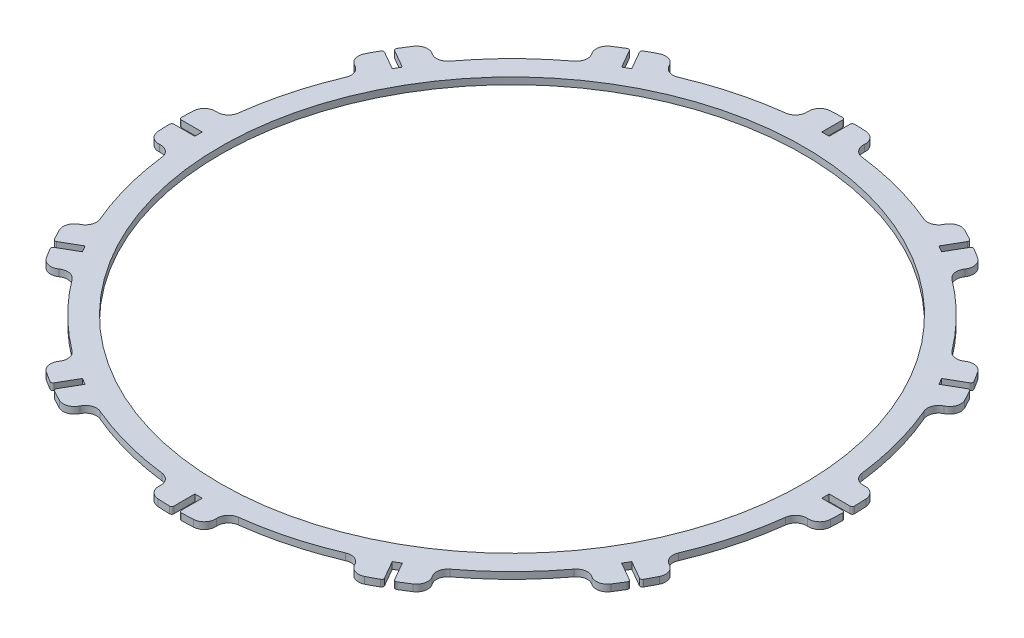
SolidWorks part; units mm, degrees
ref_plane "Front Plane" through (0, 0, 0) normal (0, 0, 1) x (1, 0, 0)
ref_plane "Top Plane" through (0, 0, 0) normal (0, 1, 0) x (1, 0, 0)
ref_plane "Right Plane" through (0, 0, 0) normal (1, 0, 0) x (0, 0, -1)
sketch "Sketch1" plane through (0, 0, 0) normal (0, 1, 0) x (1, 0, 0)
  line L1 (0, 130) -> (0, 150) construction
  circle A0 centre (0, 0) radius 150
  circle A1 centre (0, 0) radius 130
  point P7 (0, 0)
  dimension "D1" = 300
  dimension "D2" = 20
extrude "Boss-Extrude1" add sketch "Sketch1" along normal blind 3
sketch "Sketch2" plane through (0, 3, 0) normal (0, 1, 0) x (1, 0, 0)
  line L0 (0, 0) -> (0, 150) construction
  line L1 (-1.65, 139.7) -> (1.65, 139.7)
  line L2 (-1.65, 139.7) -> (-1.65, 152.3249)
  line L3 (-1.65, 152.3249) -> (1.65, 152.3249)
  line L4 (1.65, 152.3249) -> (1.65, 139.7)
  circle A0 centre (0, 0) radius 150 construction
  point P8 (0, 139.7)
  dimension "D1" = 139.7
  dimension "D2" = 3.3
extrude "Cut-Extrude1" cut sketch "Sketch2" against normal blind 3
fillet "Fillet1" radius 1 2 edges at (1.65, 1.5, -149.9909) (-1.65, 1.5, -149.9909)
pattern_circular "CirPattern1" count 12 over 360 about axis through (0, 3, 0) along (0, -1, 0) of "Fillet1", "Cut-Extrude1" reverse direction yes
sketch "Sketch3" plane through (0, 3, 0) normal (0, 1, 0) x (1, 0, 0)
  line L0 (0, 0) -> (13.0734, 149.4292) construction
  line L1 (0, 0) -> (0, 150) construction
  line L2 (0, 0) -> (69.85, 120.9837) construction
  line L3 (68.4211, 121.8087) -> (71.2789, 120.1587) construction
  line L4 (0, 0) -> (63.3927, 135.9462) construction
  line L5 (12.2018, 139.4673) -> (13.0734, 149.4292)
  line L6 (59.1666, 126.8831) -> (63.3927, 135.9462)
  arc A0 (72.6778, 131.2172) -> (2.6678, 149.9763) centre (0, 0) ccw construction
  arc A1 (12.2018, 139.4673) -> (59.1666, 126.8831) centre (0, 0) cw
  circle A2 centre (0, 0) radius 130 construction
  arc A3 (13.0734, 149.4292) -> (63.3927, 135.9462) centre (0, 0) cw
  dimension "D1" = 5
  dimension "D2" = 5
  dimension "D3" = 10
extrude "Cut-Extrude2" cut sketch "Sketch3" against normal blind 10
fillet "Fillet2" radius 5 4 edges at (63.3927, 1.5, -135.9462) (13.0734, 1.5, -149.4292) (12.2018, 1.5, -139.4673) (59.1666, 1.5, -126.8831)
pattern_circular "CirPattern2" count 12 over 360 about axis through (0, 3, 0) along (0, -1, 0) of "Cut-Extrude2", "Fillet2" reverse direction yes
equation "\"D2@Sketch3\"=\"D1@Sketch3\""
